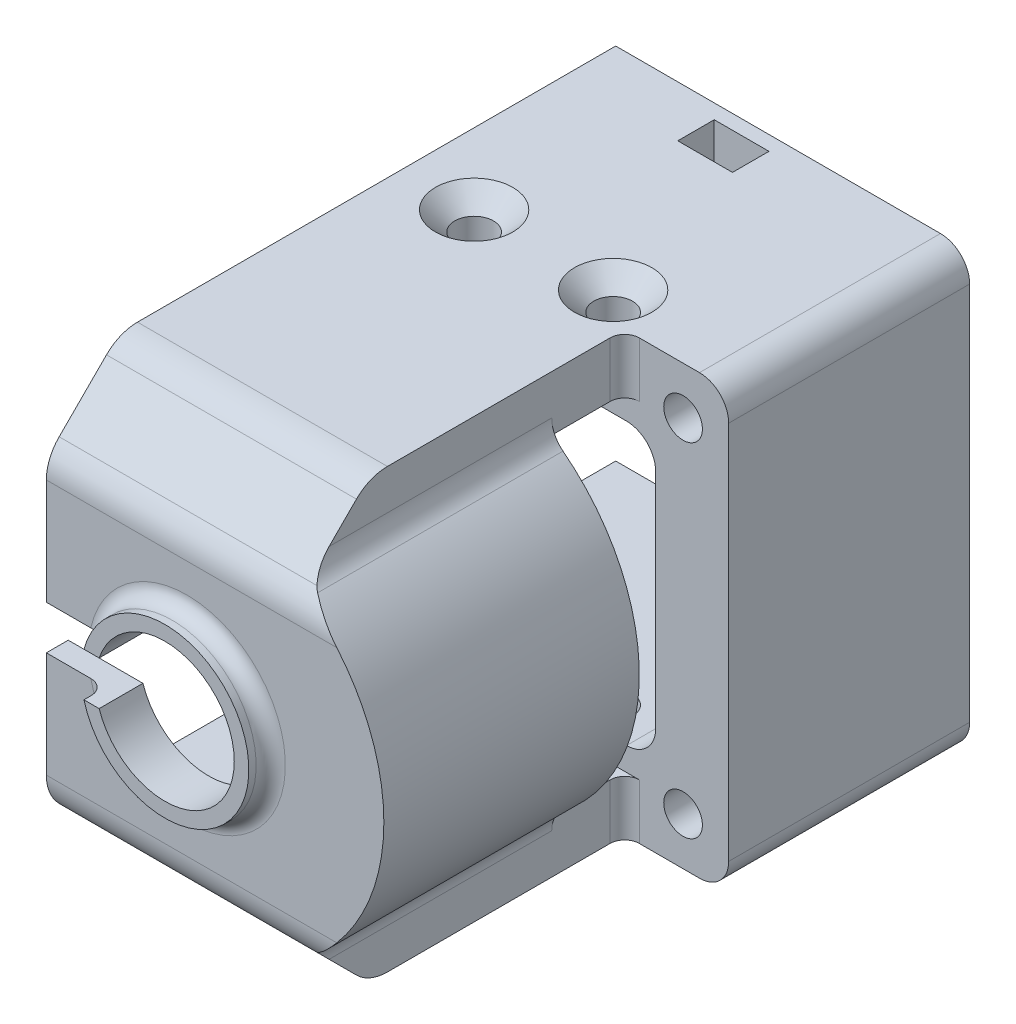
SolidWorks part; units mm, degrees
material "ABS"
ref_plane "Front Plane" through (0, 0, 0) normal (0, 0, 1) x (1, 0, 0)
ref_plane "Top Plane" through (0, 0, 0) normal (0, 1, 0) x (1, 0, 0)
ref_plane "Right Plane" through (0, 0, 0) normal (1, 0, 0) x (0, 0, -1)
sketch "Sketch1" plane through (0, 0, 0) normal (0, 0, 1) x (1, 0, 0)
  line L0 (-19.25, 19.25) -> (-19.25, 30)
  line L1 (-19.25, -19.25) -> (19.25, -19.25)
  line L3 (-19.25, 19.25) -> (19.25, 19.25)
  line L4 (19.25, -19.25) -> (19.25, 19.25)
  line L5 (-19.25, -19.25) -> (19.25, 19.25) construction
  line L6 (-19.25, 19.25) -> (19.25, -19.25) construction
  line L7 (-19.25, 30) -> (29.25, 30)
  line L8 (29.25, 30) -> (29.25, -30)
  line L9 (29.25, -30) -> (-19.25, -30)
  line L10 (-19.25, -30) -> (-19.25, -19.25)
  line L11 (0, 0) -> (19.25, 0) construction
  line L12 (19.25, 19.25) -> (29.25, 30) construction
  point P0 (0, 0)
  point P12 (23, 23.5)
  point P13 (23, -23.5)
  point P16 (24.25, 24.625)
  dimension "D1" = 38.5
  dimension "D2" = 38.5
  dimension "D3" = 60
  dimension "D4" = 10
  dimension "D5" = 23
  dimension "D6" = 6.5
extrude "Boss-Extrude1" add sketch "Sketch1" along normal mid plane 33.02
hole_wizard "M5 Clearance Hole1" positions "Sketch4" profile "Sketch5" hole size "M5" standard "ANSI Metric" end condition through all
sketch "Sketch4" plane through (0, 0, -16.51) normal (0, 0, -1) x (-1, 0, 0)
  point P4 (-23, -23.5)
  point P9 (-23, 23.5)
sketch "Sketch5" plane through (23, -23.5, -16.51) normal (1, 0, 0) x (0, 1, 0)
  line L0 (0, 0) -> (0, 33.02)
  line L1 (0, 33.02) -> (2.65, 33.02)
  line L2 (2.65, 33.02) -> (2.65, 0)
  line L5 (2.65, 0) -> (0, 0)
  line L11 (0, -6.35) -> (0, 107.95) construction
  dimension "Thru Hole Dia." = 5.3
  dimension "Thru Hole Depth" = 33.02
fillet "Fillet1" radius 4 4 edges at (29.25, -30, 0) (29.25, 30, 0) (19.25, -19.25, 0) (19.25, 19.25, 0)
sketch "Sketch6" plane through (0, 0, 16.51) normal (0, 0, 1) x (1, 0, 0)
  line L2 (-19.25, 22.5) -> (-19.25, 30)
  line L3 (-19.25, 30) -> (15, 30)
  line L4 (25.25, 30) -> (-19.25, 30) construction
  line L5 (15, 30) -> (15, 22.4499)
  line L6 (23, 28.1188) -> (19, 25.8094) construction
  line L7 (19, 25.8094) -> (19, 21.1906) construction
  line L8 (19, 21.1906) -> (23, 18.8812) construction
  line L9 (23, 18.8812) -> (27, 21.1906) construction
  line L10 (27, 21.1906) -> (27, 25.8094) construction
  line L11 (27, 25.8094) -> (23, 28.1188) construction
  line L12 (0, 0) -> (19.25, 0) construction
  line L13 (19.25, 15.25) -> (19.25, -15.25) construction
  line L15 (-19.25, -22.5) -> (-19.25, -30)
  line L16 (-19.25, -30) -> (15, -30)
  line L17 (15, -30) -> (15, -22.4499)
  line L18 (0, 22.5) -> (-19.25, 22.5)
  line L19 (0, -22.5) -> (-19.25, -22.5)
  arc A0 (0, -22.5) -> (0, 22.5) centre (0, 0) ccw
  circle A1 centre (23, 23.5) radius 4 construction
  arc A3 (15, -22.4499) -> (15, 22.4499) centre (0, 0) ccw
  dimension "D1" = 45
  dimension "D4" = 27
  dimension "D2" = 8
  dimension "D3" = 4
extrude "Boss-Extrude2" add sketch "Sketch6" along normal blind 42
sketch "Sketch7" plane through (29.25, 0, 0) normal (1, 0, 0) x (0, 0, -1)
  line L0 (-58.51, -22.4499) -> (-16.51, -22.4499) construction
  line L1 (-16.51, 22.4499) -> (-26.51, 22.4499)
  line L2 (-16.51, 22.4499) -> (-16.51, -22.4499)
  line L3 (-16.51, -22.4499) -> (-26.51, -22.4499)
  line L4 (-26.51, 22.4499) -> (-26.51, -22.4499)
  dimension "D1" = 10
extrude "Cut-Extrude1" cut sketch "Sketch7" against normal through all both and the other way through all
fillet "Fillet2" radius 4 2 edges at (15, -22.4499, 42.51) (15, 22.4499, 42.51)
sketch "Sketch8" plane through (0, 0, 58.51) normal (0, 0, 1) x (1, 0, 0)
  line L0 (-19.25, 22.5) -> (-19.25, -22.5)
  line L8 (0, -22.5) -> (-19.25, -22.5)
  line L9 (-19.25, -22.5) -> (-19.25, -30)
  line L10 (-19.25, -30) -> (15, -30)
  line L11 (15, -30) -> (15, -24.4949)
  line L12 (15, 24.4949) -> (15, 30)
  line L13 (15, 30) -> (-19.25, 30)
  line L14 (-19.25, 30) -> (-19.25, 22.5)
  line L15 (-19.25, 22.5) -> (0, 22.5)
  line L16 (0, -22.5) -> (-19.25, -22.5) construction
  line L17 (-19.25, -22.5) -> (-19.25, -30)
  line L18 (-19.25, -30) -> (15, -30)
  line L19 (15, -30) -> (15, -24.4949)
  line L20 (15, 24.4949) -> (15, 30)
  line L21 (15, 30) -> (-19.25, 30)
  line L22 (-19.25, 30) -> (-19.25, 22.5)
  line L23 (-19.25, 22.5) -> (0, 22.5) construction
  circle A0 centre (0, 0) radius 9.5
  arc A4 (0, -22.5) -> (0, 22.5) centre (0, 0) ccw
  arc A5 (16.5484, -21.3343) -> (15, -24.4949) centre (19, -24.4949) ccw
  arc A6 (16.5484, -21.3343) -> (16.5484, 21.3343) centre (0, 0) ccw
  arc A7 (15, 24.4949) -> (16.5484, 21.3343) centre (19, 24.4949) ccw
  arc A8 (0, -22.5) -> (0, 22.5) centre (0, 0) ccw construction
  arc A9 (16.5484, -21.3343) -> (15, -24.4949) centre (19, -24.4949) ccw
  arc A10 (16.5484, -21.3343) -> (16.5484, 21.3343) centre (0, 0) ccw
  arc A11 (15, 24.4949) -> (16.5484, 21.3343) centre (19, 24.4949) ccw
  dimension "D2" = 19
  dimension "D1" = 0
extrude "Boss-Extrude3" add sketch "Sketch8" along normal blind 3
sketch "Sketch9" plane through (0, 30, 0) normal (0, 1, 0) x (1, 0, 0)
  line L0 (25.25, -16.51) -> (15, -16.51) construction
  line L1 (-19.05, -16.51) -> (19.05, -16.51) construction
  line L2 (-19.05, -16.51) -> (-19.05, -8.7225) construction
  line L3 (-19.05, -8.7225) -> (19.05, -8.7225) construction
  line L4 (19.05, -16.51) -> (19.05, -8.7225) construction
  line L5 (-19.05, -16.51) -> (19.05, -8.7225) construction
  line L6 (-19.05, -8.7225) -> (19.05, -16.51) construction
  line L7 (-19.25, -61.51) -> (-19.25, 16.51) construction
  line L8 (0, -12.6163) -> (0, -8.7225) construction
  point P0 (0, -12.6162)
  point P11 (-9.525, -12.6163)
  point P12 (9.525, -12.6163)
  dimension "D1" = 7.7875
  dimension "D2" = 38.1
  dimension "D3" = 0.2
  dimension "D4" = 19.05
hole_wizard "CSK for M5 Flat Head Machine Screw1" positions "Sketch10" profile "Sketch11" countersink size "M5" standard "ANSI Metric" end condition up to next
sketch "Sketch10" plane through (0, 30, 0) normal (0, 1, 0) x (1, 0, 0)
  point P0 (-9.525, -12.6163)
  point P3 (9.525, -12.6163)
sketch "Sketch11" plane through (-9.525, 30, 12.6163) normal (1, 0, 0) x (0, 0, 1)
  line L0 (0, 0) -> (0, 10.75)
  line L1 (0, 10.75) -> (2.65, 10.75)
  line L2 (2.65, 10.75) -> (2.65, 2.65)
  line L3 (2.65, 2.65) -> (5.3, 0)
  line L5 (5.3, 0) -> (0, 0)
  line L6 (-2.65, 2.65) -> (-5.3, 0) construction
  line L11 (0, -6.35) -> (0, 107.95) construction
  dimension "Thru Hole Dia." = 5.3
  dimension "Thru Hole Depth" = 10.75
  dimension "Near C'Sink Dia." = 10.6
  dimension "Near C'Sink Angle" = 90
mirror "Mirror1" about plane through (0, 0, 0) normal (0, 1, 0) of "CSK for M5 Flat Head Machine Screw1"
chamfer "Chamfer1" distance 10 angle 45 2 edges at (-2.125, -30, 61.51) (-2.125, 30, 61.51)
fillet "Fillet5" radius 6 7 edges at (-9.625, 22.5, 58.51) (22.5, 0, 58.51) (-9.625, -22.5, 58.51) (-2.125, 30, 51.51) (-0.5558, 20, 61.51) (-2.125, -30, 51.51) (-0.5558, -20, 61.51)
ref_plane "Plane1" through (0, 0, -14.51) normal (0, 0, -1) x (-1, 0, 0)
sketch "Sketch12" plane through (0, 0, -14.51) normal (0, 0, -1) x (-1, 0, 0)
  line L0 (-3.75, 25.1651) -> (-3.75, 30)
  line L1 (0, 27.3301) -> (-3.75, 25.1651) construction
  line L2 (-3.75, 25.1651) -> (-3.75, 20.8349)
  line L3 (-3.75, 20.8349) -> (0, 18.6699)
  line L4 (0, 18.6699) -> (3.75, 20.8349)
  line L5 (3.75, 20.8349) -> (3.75, 25.1651)
  line L6 (3.75, 25.1651) -> (0, 27.3301) construction
  line L7 (3.75, 25.1651) -> (3.75, 30)
  line L8 (-3.75, 30) -> (3.75, 30)
  line L9 (-25.25, 30) -> (19.25, 30) construction
  circle A0 centre (0, 23) radius 3.75 construction
  point P1 (-3.75, 32.8639)
  dimension "D1" = 7.5
  dimension "D2" = 23
extrude "Cut-Extrude2" cut sketch "Sketch12" against normal blind 5
mirror "Mirror2" about plane through (0, 0, 0) normal (0, 1, 0) of "Cut-Extrude2"
sketch "Sketch13" plane through (0, 0, -16.51) normal (0, 0, -1) x (-1, 0, 0)
  line L0 (0, 0) -> (19.25, 0) construction
  line L1 (19.25, 16.5) -> (19.25, -16.5) construction
  point P0 (0, 23)
  point P6 (0, -23)
  dimension "D1" = 23
hole_wizard "M4 Clearance Hole1" positions "Sketch14" profile "Sketch15" hole size "M4" standard "ANSI Metric" end condition up to next
sketch "Sketch14" plane through (0, 0, -16.51) normal (0, 0, -1) x (-1, 0, 0)
  point P0 (0, 23)
  point P3 (0, -23)
sketch "Sketch15" plane through (0, 23, -16.51) normal (1, 0, 0) x (0, 1, 0)
  line L0 (0, 0) -> (0, 2)
  line L1 (0, 2) -> (2.15, 2)
  line L2 (2.15, 2) -> (2.15, 0)
  line L5 (2.15, 0) -> (0, 0)
  line L11 (0, -6.35) -> (0, 107.95) construction
  dimension "Thru Hole Dia." = 4.3
  dimension "Thru Hole Depth" = 2
sketch "Sketch16" plane through (0, 0, 61.51) normal (0, 0, 1) x (1, 0, 0)
  circle A0 centre (0, 0) radius 11.5
  circle A1 centre (0, 0) radius 9.5
  dimension "D1" = 2
  dimension "D2" = 19
extrude "Boss-Extrude4" add sketch "Sketch16" along normal blind 3
fillet "Fillet6" radius 2 3 edges at (11.5, 0, 61.51) (15, -26.225, 16.51) (15, 26.225, 16.51)
sketch "Sketch17" plane through (0, 0, 64.51) normal (0, 0, 1) x (1, 0, 0)
  line L0 (0, 3) -> (-19.25, 3)
  line L1 (-19.25, 17.5147) -> (-19.25, -17.5147) construction
  line L2 (-19.25, 3) -> (-19.25, -3)
  line L3 (-19.25, -3) -> (0, -3)
  arc A0 (0, -3) -> (0, 3) centre (0, 0) ccw
  dimension "D1" = 6
extrude "Cut-Extrude3" cut sketch "Sketch17" against normal through all
equation "\"D1@Boss-Extrude1\"=1.3in"
equation "\"D4@Sketch9\"=0.75in"
